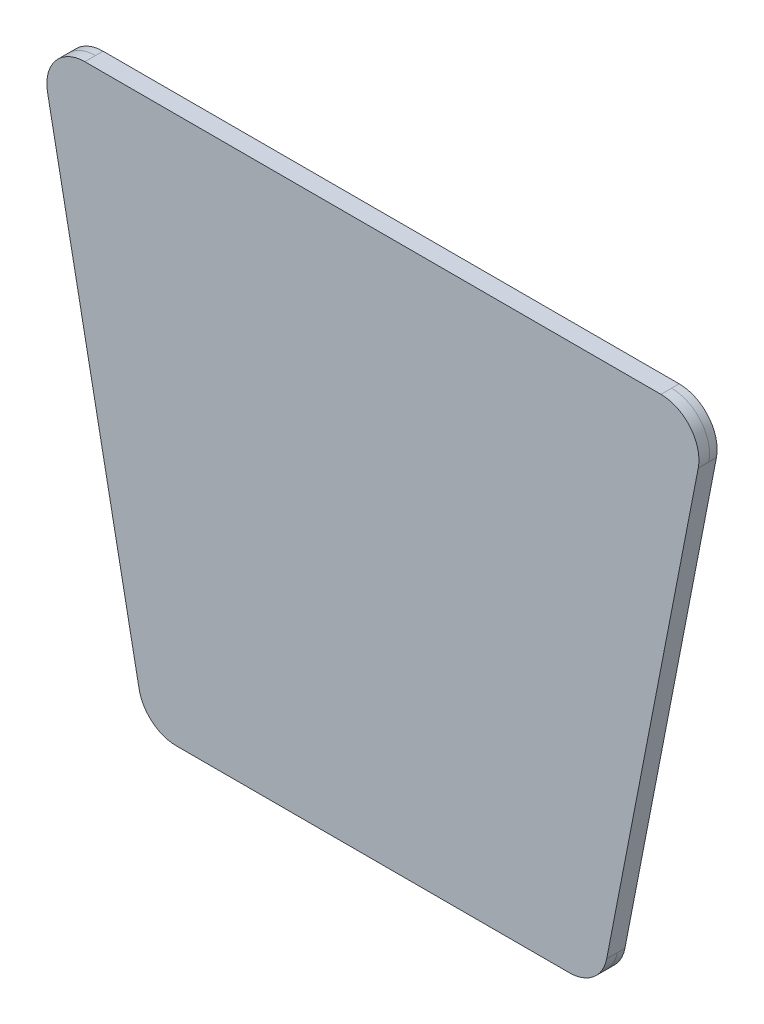
SolidWorks part; units mm, degrees
material "ABS PC"
ref_plane "Front Plane" through (0, 0, 0) normal (0, 0, 1) x (1, 0, 0)
ref_plane "Top Plane" through (0, 0, 0) normal (0, 1, 0) x (1, 0, 0)
ref_plane "Right Plane" through (0, 0, 0) normal (1, 0, 0) x (0, 0, -1)
sketch "Sketch1" plane through (0, 0, 0) normal (0, 0, 1) x (1, 0, 0)
  line L0 (-220, 0) -> (220, 0)
  line L1 (220, 0) -> (150, -360)
  line L2 (150, -360) -> (-150, -360)
  line L3 (-150, -360) -> (-220, 0)
  line L4 (0, 290.8745) -> (0, -449.6578) construction
  point P7 (185, -180)
  point P8 (-185, -180)
  dimension "D1" = 360
  dimension "D2" = 370
  dimension "D3" = 440
extrude "Boss-Extrude2" add sketch "Sketch1" along normal blind 12 contours L3 L0 L1 L2
fillet "Fillet1" radius 25 4 edges at (220, 0, 6) (150, -360, 6) (-220, 0, 6) (-150, -360, 6)
sketch "Sketch3" plane through (0, 0, 0) normal (0, 0, -1) x (-1, 0, 0)
  line L0 (189.6707, -2) -> (-189.6707, -2)
  line L1 (-212.2478, -29.39) -> (-151.97, -339.39)
  line L2 (-129.3929, -358) -> (129.3929, -358)
  line L3 (151.97, -339.39) -> (212.2478, -29.39)
  line L4 (189.6707, 0) -> (-189.6707, 0)
  line L5 (-214.2111, -29.7717) -> (-153.9333, -339.7717)
  line L6 (-129.3929, -360) -> (129.3929, -360)
  line L7 (153.9333, -339.7717) -> (214.2111, -29.7717)
  line L8 (189.6707, 0) -> (-189.6707, 0)
  line L9 (-214.2111, -29.7717) -> (-153.9333, -339.7717)
  line L10 (-129.3929, -360) -> (129.3929, -360)
  line L11 (153.9333, -339.7717) -> (214.2111, -29.7717)
  arc A0 (-189.6707, -2) -> (-212.2478, -29.39) centre (-189.6707, -25) ccw
  arc A1 (-151.97, -339.39) -> (-129.3929, -358) centre (-129.3929, -335) ccw
  arc A2 (129.3929, -358) -> (151.97, -339.39) centre (129.3929, -335) ccw
  arc A3 (212.2478, -29.39) -> (189.6707, -2) centre (189.6707, -25) ccw
  arc A4 (-189.6707, 0) -> (-214.2111, -29.7717) centre (-189.6707, -25) ccw
  arc A5 (-153.9333, -339.7717) -> (-129.3929, -360) centre (-129.3929, -335) ccw
  arc A6 (129.3929, -360) -> (153.9333, -339.7717) centre (129.3929, -335) ccw
  arc A7 (214.2111, -29.7717) -> (189.6707, 0) centre (189.6707, -25) ccw
  arc A8 (-189.6707, 0) -> (-214.2111, -29.7717) centre (-189.6707, -25) ccw
  arc A9 (-153.9333, -339.7717) -> (-129.3929, -360) centre (-129.3929, -335) ccw
  arc A10 (129.3929, -360) -> (153.9333, -339.7717) centre (129.3929, -335) ccw
  arc A11 (214.2111, -29.7717) -> (189.6707, 0) centre (189.6707, -25) ccw
  dimension "D1" = 0
  dimension "D2" = 2
extrude "Cut-Extrude1" cut sketch "Sketch3" against normal blind 10 contours L0 A0 L1 A1 L2 A2 L3 A3
sketch "Sketch4" plane through (0, 0, 10) normal (0, 0, -1) x (-1, 0, 0)
  circle A0 centre (-189.6707, -25) radius 23
  circle A1 centre (-189.6707, -25) radius 19
  dimension "D1" = 38
extrude "Boss-Extrude5" add sketch "Sketch4" along normal blind 10
sketch "Sketch5" plane through (0, 0, 10) normal (0, 0, -1) x (-1, 0, 0)
  circle A0 centre (-129.3929, -335) radius 23
  circle A1 centre (-129.3929, -335) radius 19
  dimension "D1" = 38
extrude "Boss-Extrude6" add sketch "Sketch5" along normal blind 10
mirror "Mirror1" about plane through (0, 0, 0) normal (1, 0, 0) of "Boss-Extrude6", "Boss-Extrude5"
ref_plane "Plane1" through (0, 0, 6) normal (0, 0, 1) x (1, 0, 0)
sketch "Sketch9" plane through (0, 0, 6) normal (0, 0, 1) x (1, 0, 0)
  line L0 (-182.9625, -180) -> (182.9625, -180) construction
  line L1 (25, -180) -> (17.6777, -162.3223) construction
  line L2 (17.6777, -162.3223) -> (0, -155) construction
  line L3 (0, -155) -> (-17.6777, -162.3223) construction
  line L4 (-17.6777, -162.3223) -> (-25, -180) construction
  line L5 (-25, -180) -> (-17.6777, -197.6777) construction
  line L6 (-17.6777, -197.6777) -> (0, -205) construction
  line L7 (0, -205) -> (17.6777, -197.6777) construction
  line L8 (17.6777, -197.6777) -> (25, -180) construction
  line L9 (0, -358) -> (0, -2) construction
  line L12 (-1, -2) -> (-1, -358)
  line L13 (1, -2) -> (1, -358)
  line L14 (-179.4142, -2) -> (130.6185, -312.0327)
  line L15 (-132.168, -312.168) -> (178, -2) construction
  line L16 (176.5858, -2) -> (-133.8503, -312.4361)
  line L17 (179.4142, -2) -> (-130.6185, -312.0327)
  line L18 (182.7681, -181) -> (-182.7681, -181)
  line L19 (-183.157, -179) -> (183.157, -179)
  line L20 (129.3929, -358) -> (-129.3929, -358) construction
  line L21 (-151.97, -339.39) -> (-212.2478, -29.39) construction
  line L22 (-189.6707, -2) -> (189.6707, -2) construction
  line L23 (212.2478, -29.39) -> (151.97, -339.39) construction
  line L24 (129.3929, -358) -> (-129.3929, -358)
  line L25 (-151.97, -339.39) -> (-212.2478, -29.39)
  line L26 (-189.6707, -2) -> (189.6707, -2)
  line L27 (212.2478, -29.39) -> (151.97, -339.39)
  line L29 (132.6318, -312.2292) -> (-184.3863, 4.7889) construction
  line L30 (133.8503, -312.4361) -> (-176.5858, -2)
  circle A0 centre (0, -180) radius 23.097 construction
  arc A1 (151.97, -339.39) -> (129.3929, -358) centre (129.3929, -335) ccw construction
  arc A2 (-129.3929, -358) -> (-151.97, -339.39) centre (-129.3929, -335) ccw construction
  arc A3 (-212.2478, -29.39) -> (-189.6707, -2) centre (-189.6707, -25) ccw construction
  arc A4 (189.6707, -2) -> (212.2478, -29.39) centre (189.6707, -25) ccw construction
  arc A5 (151.97, -339.39) -> (129.3929, -358) centre (129.3929, -335) ccw
  arc A6 (-129.3929, -358) -> (-151.97, -339.39) centre (-129.3929, -335) ccw
  arc A7 (-212.2478, -29.39) -> (-189.6707, -2) centre (-189.6707, -25) ccw
  arc A8 (189.6707, -2) -> (212.2478, -29.39) centre (189.6707, -25) ccw
  point P14 (0, -180)
  point P17 (0, -180)
  point P20 (0, -180)
  point P23 (0, -180)
  dimension "D1" = 180
  dimension "D2" = 25
  dimension "D3" = 2
  dimension "D4" = 2
  dimension "D5" = 2
  dimension "D6" = 2
  dimension "D7" = 130.6185
extrude "Boss-Extrude9" add sketch "Sketch9" along normal up to surface (4 mm away) contours L13 L30 L19 L16 L12 L14 L18 L17 | L19 L30 L16 | L30 L13 L19 | L17 L30 L13 | L17 L18 L14 | L18 L14 L12 | L12 L16 L14 | L14 L18 L12 L17 | L18 L12 L14 L16 | L19 L14 L16 L12 | L19 L12 L16 | L16 L30 L12 L19 | L30 L19 L13 L16 | L30 L17 L19 L13 | L18 L30 L17 L13 | L18 L13 L17 | L13 L18 L17 L14 | A5 L30 L18 L13 L14 | L24 L13 L14 L17 L12 | A6 L17 L12 L18 L16 | L25 L18 L16 L14 L19 | L12 L30 L26 L14 L19 | L30 L16 L13 L26 L12 | L26 L16 L13 L19 L17 | L30 L18 L27 L19 L17 region at (0, -90.0431, 6) region at (-0.6381, -178.4596, 6) region at (-89.6781, -90.3238, 6) region at (-0.8047, -179.1953, 6) region at (-1.5404, -179.3619, 6) region at (0, -178.8619, 6) region at (0.6381, -178.4596, 6) region at (89.6781, -90.3238, 6) region at (0, -180, 6) region at (-1.1381, -180, 6) region at (-92.4382, -179.9996, 6) region at (0.8047, -179.1953, 6) region at (1.5404, -179.3619, 6) region at (-0.8047, -180.8047, 6) region at (-1.5404, -180.6381, 6) region at (1.1381, -180, 6) region at (92.4382, -179.9996, 6) region at (-0.6381, -181.5404, 6) region at (-66.7743, -246.7711, 6) region at (0, -181.1381, 6) region at (1.5404, -180.6381, 6) region at (0.8047, -180.8047, 6) region at (0, -269.9569, 6) region at (0.6381, -181.5404, 6) region at (66.7743, -246.7711, 6) up to face at (0, -180.3179, 10)
sketch "Sketch10" plane through (0, 0, 6) normal (0, 0, 1) x (1, 0, 0)
  line L0 (182.7681, -181) -> (-182.7681, -181) construction
  line L1 (179.4142, -2) -> (-130.6185, -312.0327) construction
  line L2 (-183.157, -179) -> (183.157, -179) construction
  line L3 (176.5858, -2) -> (-133.8503, -312.4361) construction
  line L4 (-212.2478, -29.39) -> (-151.97, -339.39)
  line L5 (-129.3929, -358) -> (129.3929, -358)
  line L6 (151.97, -339.39) -> (212.2478, -29.39)
  line L7 (189.6707, -2) -> (-189.6707, -2)
  line L8 (-212.2478, -29.39) -> (-151.97, -339.39)
  line L9 (-129.3929, -358) -> (129.3929, -358)
  line L10 (151.97, -339.39) -> (212.2478, -29.39)
  line L11 (189.6707, -2) -> (-189.6707, -2)
  line L12 (-179.4142, -2) -> (130.6185, -312.0327) construction
  line L13 (1, -2) -> (1, -358) construction
  line L14 (-1, -2) -> (-1, -358) construction
  line L15 (133.8503, -312.4361) -> (-176.5858, -2) construction
  line L16 (182.7681, -181) -> (-182.7681, -181)
  line L17 (179.4142, -2) -> (-130.6185, -312.0327)
  line L18 (-183.157, -179) -> (183.157, -179)
  line L19 (176.5858, -2) -> (-133.8503, -312.4361)
  line L20 (-179.4142, -2) -> (130.6185, -312.0327)
  line L21 (1, -2) -> (1, -358)
  line L22 (-1, -2) -> (-1, -358)
  line L23 (133.8503, -312.4361) -> (-176.5858, -2)
  line L24 (0, 33.3188) -> (0, -390.4492) construction
  line L25 (189.9291, -180) -> (-188.2058, -180) construction
  line L26 (-189.6707, 0) -> (189.6707, 0) construction
  line L36 (0, -151.8578) -> (-19.8995, -160.1005) construction
  line L37 (-19.8995, -160.1005) -> (-28.1422, -180) construction
  line L38 (-28.1422, -180) -> (-19.8995, -199.8995) construction
  line L39 (-19.8995, -199.8995) -> (0, -208.1422) construction
  line L40 (0, -208.1422) -> (19.8995, -199.8995) construction
  line L41 (19.8995, -199.8995) -> (28.1422, -180) construction
  line L42 (28.1422, -180) -> (19.8995, -160.1005) construction
  line L43 (19.8995, -160.1005) -> (0, -151.8578) construction
  line L44 (0, -154.0226) -> (-18.3688, -161.6312) construction
  line L45 (-18.3688, -161.6312) -> (-25.9774, -180) construction
  line L46 (-25.9774, -180) -> (-18.3688, -198.3688) construction
  line L47 (-18.3688, -198.3688) -> (0, -205.9774) construction
  line L48 (0, -205.9774) -> (18.3688, -198.3688) construction
  line L49 (18.3688, -198.3688) -> (25.9774, -180) construction
  line L50 (25.9774, -180) -> (18.3688, -161.6312) construction
  line L51 (18.3688, -161.6312) -> (0, -154.0226) construction
  line L52 (0, -137.7867) -> (-29.8493, -150.1507) construction
  line L53 (-29.8493, -150.1507) -> (-42.2133, -180) construction
  line L54 (-42.2133, -180) -> (-29.8493, -209.8493) construction
  line L55 (-29.8493, -209.8493) -> (0, -222.2133) construction
  line L56 (0, -222.2133) -> (29.8493, -209.8493) construction
  line L57 (29.8493, -209.8493) -> (42.2133, -180) construction
  line L58 (42.2133, -180) -> (29.8493, -150.1507) construction
  line L59 (29.8493, -150.1507) -> (0, -137.7867) construction
  line L60 (0, -135.6219) -> (-31.38, -148.62) construction
  line L61 (-31.38, -148.62) -> (-44.3781, -180) construction
  line L62 (-44.3781, -180) -> (-31.38, -211.38) construction
  line L63 (-31.38, -211.38) -> (0, -224.3781) construction
  line L64 (0, -224.3781) -> (31.38, -211.38) construction
  line L65 (31.38, -211.38) -> (44.3781, -180) construction
  line L66 (44.3781, -180) -> (31.38, -148.62) construction
  line L67 (31.38, -148.62) -> (0, -135.6219) construction
  line L68 (0, -116.1389) -> (-45.1566, -134.8434) construction
  line L69 (-45.1566, -134.8434) -> (-63.8611, -180) construction
  line L70 (-63.8611, -180) -> (-45.1566, -225.1566) construction
  line L71 (-45.1566, -225.1566) -> (0, -243.8611) construction
  line L72 (0, -243.8611) -> (45.1566, -225.1566) construction
  line L73 (45.1566, -225.1566) -> (63.8611, -180) construction
  line L74 (63.8611, -180) -> (45.1566, -134.8434) construction
  line L75 (45.1566, -134.8434) -> (0, -116.1389) construction
  line L76 (-66.0259, -180) -> (-46.6874, -226.6874) construction
  line L77 (-46.6874, -226.6874) -> (0, -246.0259) construction
  line L78 (0, -246.0259) -> (46.6874, -226.6874) construction
  line L79 (46.6874, -226.6874) -> (66.0259, -180) construction
  line L80 (66.0259, -180) -> (46.6874, -133.3126) construction
  line L81 (46.6874, -133.3126) -> (0, -113.9741) construction
  line L82 (0, -113.9741) -> (-46.6874, -133.3126) construction
  line L83 (-46.6874, -133.3126) -> (-66.0259, -180) construction
  line L84 (0, -83.6671) -> (-68.1177, -111.8823) construction
  line L85 (-68.1177, -111.8823) -> (-96.3329, -180) construction
  line L86 (-96.3329, -180) -> (-68.1177, -248.1177) construction
  line L87 (-68.1177, -248.1177) -> (0, -276.3329) construction
  line L88 (0, -276.3329) -> (68.1177, -248.1177) construction
  line L89 (68.1177, -248.1177) -> (96.3329, -180) construction
  line L90 (96.3329, -180) -> (68.1177, -111.8823) construction
  line L91 (68.1177, -111.8823) -> (0, -83.6671) construction
  line L92 (0, -81.5023) -> (-69.6484, -110.3516) construction
  line L93 (-69.6484, -110.3516) -> (-98.4977, -180) construction
  line L94 (-98.4977, -180) -> (-69.6484, -249.6484) construction
  line L95 (-69.6484, -249.6484) -> (0, -278.4977) construction
  line L96 (0, -278.4977) -> (69.6484, -249.6484) construction
  line L97 (69.6484, -249.6484) -> (98.4977, -180) construction
  line L98 (98.4977, -180) -> (69.6484, -110.3516) construction
  line L99 (69.6484, -110.3516) -> (0, -81.5023) construction
  line L100 (0, -40.3714) -> (-98.7323, -81.2677) construction
  line L101 (-98.7323, -81.2677) -> (-139.6286, -180) construction
  line L102 (-139.6286, -180) -> (-98.7323, -278.7323) construction
  line L103 (-98.7323, -278.7323) -> (0, -319.6286) construction
  line L104 (0, -319.6286) -> (98.7323, -278.7323) construction
  line L105 (98.7323, -278.7323) -> (139.6286, -180) construction
  line L106 (139.6286, -180) -> (98.7323, -81.2677) construction
  line L107 (98.7323, -81.2677) -> (0, -40.3714) construction
  line L108 (0, -38.2066) -> (-100.2631, -79.7369) construction
  line L109 (-100.2631, -79.7369) -> (-141.7934, -180) construction
  line L110 (-141.7934, -180) -> (-100.2631, -280.2631) construction
  line L111 (-100.2631, -280.2631) -> (0, -321.7934) construction
  line L112 (0, -321.7934) -> (100.2631, -280.2631) construction
  line L113 (100.2631, -280.2631) -> (141.7934, -180) construction
  line L114 (141.7934, -180) -> (100.2631, -79.7369) construction
  line L115 (100.2631, -79.7369) -> (0, -38.2066) construction
  line L116 (0, -7.8996) -> (-121.6933, -58.3067) construction
  line L117 (-121.6933, -58.3067) -> (-172.1004, -180) construction
  line L118 (-172.1004, -180) -> (-121.6933, -301.6933) construction
  line L119 (-121.6933, -301.6933) -> (0, -352.1004) construction
  line L120 (0, -352.1004) -> (121.6933, -301.6933) construction
  line L121 (121.6933, -301.6933) -> (172.1004, -180) construction
  line L122 (172.1004, -180) -> (121.6933, -58.3067) construction
  line L123 (121.6933, -58.3067) -> (0, -7.8996) construction
  line L124 (0, -5.7349) -> (-123.2241, -56.7759) construction
  line L125 (-123.2241, -56.7759) -> (-174.2651, -180) construction
  line L126 (-174.2651, -180) -> (-123.2241, -303.2241) construction
  line L127 (-123.2241, -303.2241) -> (0, -354.2651) construction
  line L128 (0, -354.2651) -> (123.2241, -303.2241) construction
  line L129 (123.2241, -303.2241) -> (174.2651, -180) construction
  line L130 (174.2651, -180) -> (123.2241, -56.7759) construction
  line L131 (123.2241, -56.7759) -> (0, -5.7349) construction
  arc A0 (0, -151.8578) -> (-19.8995, -160.1005) centre (-31.9509, -102.8638) cw
  circle A1 centre (0, -180) radius 26 construction
  circle A2 centre (0, -180) radius 24 construction
  arc A3 (0, -154.0226) -> (-18.3688, -161.6312) centre (-27.9026, -112.6372) cw
  arc A4 (-129.3929, -358) -> (-151.97, -339.39) centre (-129.3929, -335) ccw
  arc A5 (151.97, -339.39) -> (129.3929, -358) centre (129.3929, -335) ccw
  arc A6 (189.6707, -2) -> (212.2478, -29.39) centre (189.6707, -25) ccw
  arc A7 (-212.2478, -29.39) -> (-189.6707, -2) centre (-189.6707, -25) ccw
  arc A8 (-129.3929, -358) -> (-151.97, -339.39) centre (-129.3929, -335) ccw
  arc A9 (151.97, -339.39) -> (129.3929, -358) centre (129.3929, -335) ccw
  arc A10 (189.6707, -2) -> (212.2478, -29.39) centre (189.6707, -25) ccw
  arc A11 (-212.2478, -29.39) -> (-189.6707, -2) centre (-189.6707, -25) ccw
  arc A12 (0, -151.8578) -> (19.8995, -160.1005) centre (31.9509, -102.8638) ccw
  arc A13 (18.3688, -161.6312) -> (0, -154.0226) centre (27.9026, -112.6372) cw
  arc A14 (18.3688, -161.6312) -> (25.9774, -180) centre (67.3628, -152.0974) ccw
  arc A15 (25.9774, -180) -> (18.3688, -198.3688) centre (67.3628, -207.9026) ccw
  arc A16 (18.3688, -198.3688) -> (0, -205.9774) centre (27.9026, -247.3628) ccw
  arc A17 (0, -205.9774) -> (-18.3688, -198.3688) centre (-27.9026, -247.3628) ccw
  arc A18 (-18.3688, -198.3688) -> (-25.9774, -180) centre (-67.3628, -207.9026) ccw
  arc A19 (-25.9774, -180) -> (-18.3688, -161.6312) centre (-67.3628, -152.0974) ccw
  arc A20 (-19.8995, -160.1005) -> (-28.1422, -180) centre (-77.1362, -148.0491) cw
  arc A21 (-28.1422, -180) -> (-19.8995, -199.8995) centre (-77.1362, -211.9509) cw
  arc A22 (-19.8995, -199.8995) -> (0, -208.1422) centre (-31.9509, -257.1362) cw
  arc A23 (0, -208.1422) -> (19.8995, -199.8995) centre (31.9509, -257.1362) cw
  arc A24 (19.8995, -199.8995) -> (28.1422, -180) centre (77.1362, -211.9509) cw
  arc A25 (28.1422, -180) -> (19.8995, -160.1005) centre (77.1362, -148.0491) cw
  circle A26 centre (0, -180) radius 39 construction
  circle A27 centre (0, -180) radius 41 construction
  arc A28 (0, -135.6219) -> (-31.38, -148.62) centre (-70.6843, -9.353) cw
  arc A29 (-31.38, -148.62) -> (-44.3781, -180) centre (-170.647, -109.3157) cw
  arc A30 (-44.3781, -180) -> (-31.38, -211.38) centre (-170.647, -250.6843) cw
  arc A31 (-31.38, -211.38) -> (0, -224.3781) centre (-70.6843, -350.647) cw
  arc A32 (0, -224.3781) -> (31.38, -211.38) centre (70.6843, -350.647) cw
  arc A33 (31.38, -211.38) -> (44.3781, -180) centre (170.647, -250.6843) cw
  arc A34 (44.3781, -180) -> (31.38, -148.62) centre (170.647, -109.3157) cw
  arc A35 (31.38, -148.62) -> (0, -135.6219) centre (70.6843, -9.353) cw
  arc A36 (0, -137.7867) -> (-29.8493, -150.1507) centre (-64.6663, -23.8818) cw
  arc A37 (-29.8493, -150.1507) -> (-42.2133, -180) centre (-156.1182, -115.3337) cw
  arc A38 (-42.2133, -180) -> (-29.8493, -209.8493) centre (-156.1182, -244.6663) cw
  arc A39 (-29.8493, -209.8493) -> (0, -222.2133) centre (-64.6663, -336.1182) cw
  arc A40 (0, -222.2133) -> (29.8493, -209.8493) centre (64.6663, -336.1182) cw
  arc A41 (29.8493, -209.8493) -> (42.2133, -180) centre (156.1182, -244.6663) cw
  arc A42 (42.2133, -180) -> (29.8493, -150.1507) centre (156.1182, -115.3337) cw
  arc A43 (29.8493, -150.1507) -> (0, -137.7867) centre (64.6663, -23.8818) cw
  circle A44 centre (0, -180) radius 59 construction
  circle A45 centre (0, -180) radius 61 construction
  arc A46 (0, -113.9741) -> (-46.6874, -133.3126) centre (-145.3092, 170.8075) cw
  arc A47 (-46.6874, -133.3126) -> (-66.0259, -180) centre (-350.8075, -34.6908) cw
  arc A48 (-66.0259, -180) -> (-46.6874, -226.6874) centre (-350.8075, -325.3092) cw
  arc A49 (-46.6874, -226.6874) -> (0, -246.0259) centre (-145.3092, -530.8075) cw
  arc A50 (0, -246.0259) -> (46.6874, -226.6874) centre (145.3092, -530.8075) cw
  arc A51 (46.6874, -226.6874) -> (66.0259, -180) centre (350.8075, -325.3092) cw
  arc A52 (66.0259, -180) -> (46.6874, -133.3126) centre (350.8075, -34.6908) cw
  arc A53 (46.6874, -133.3126) -> (0, -113.9741) centre (145.3092, 170.8075) cw
  arc A54 (0, -116.1389) -> (-45.1566, -134.8434) centre (-136.6649, 149.9383) cw
  arc A55 (-45.1566, -134.8434) -> (-63.8611, -180) centre (-329.9383, -43.3351) cw
  arc A56 (-63.8611, -180) -> (-45.1566, -225.1566) centre (-329.9383, -316.6649) cw
  arc A57 (-45.1566, -225.1566) -> (0, -243.8611) centre (-136.6649, -509.9383) cw
  arc A58 (0, -243.8611) -> (45.1566, -225.1566) centre (136.6649, -509.9383) cw
  arc A59 (45.1566, -225.1566) -> (63.8611, -180) centre (329.9383, -316.6649) cw
  arc A60 (63.8611, -180) -> (45.1566, -134.8434) centre (329.9383, -43.3351) cw
  arc A61 (45.1566, -134.8434) -> (0, -116.1389) centre (136.6649, 149.9383) cw
  circle A62 centre (0, -180) radius 89 construction
  circle A63 centre (0, -180) radius 91 construction
  arc A64 (0, -81.5023) -> (-69.6484, -110.3516) centre (-306.4902, 559.9328) cw
  arc A65 (-69.6484, -110.3516) -> (-98.4977, -180) centre (-739.9328, 126.4902) cw
  arc A66 (-98.4977, -180) -> (-69.6484, -249.6484) centre (-739.9328, -486.4902) cw
  arc A67 (-69.6484, -249.6484) -> (0, -278.4977) centre (-306.4902, -919.9328) cw
  arc A68 (0, -276.3329) -> (-68.1177, -248.1177) centre (-293.9064, -889.5528) ccw
  arc A69 (-68.1177, -248.1177) -> (-96.3329, -180) centre (-709.5528, -473.9064) ccw
  arc A70 (-96.3329, -180) -> (-68.1177, -111.8823) centre (-709.5528, 113.9064) ccw
  arc A71 (-68.1177, -111.8823) -> (0, -83.6671) centre (-293.9064, 529.5528) ccw
  arc A72 (69.6484, -249.6484) -> (0, -278.4977) centre (306.4902, -919.9328) ccw
  arc A73 (0, -276.3329) -> (68.1177, -248.1177) centre (293.9064, -889.5528) cw
  arc A74 (68.1177, -248.1177) -> (96.3329, -180) centre (709.5528, -473.9064) cw
  arc A75 (98.4977, -180) -> (69.6484, -249.6484) centre (739.9328, -486.4902) ccw
  arc A76 (69.6484, -110.3516) -> (98.4977, -180) centre (739.9328, 126.4902) ccw
  arc A77 (96.3329, -180) -> (68.1177, -111.8823) centre (709.5528, 113.9064) cw
  arc A78 (68.1177, -111.8823) -> (0, -83.6671) centre (293.9064, 529.5528) cw
  arc A79 (0, -81.5023) -> (69.6484, -110.3516) centre (306.4902, 559.9328) ccw
  circle A80 centre (0, -180) radius 129 construction
  circle A81 centre (0, -180) radius 131 construction
  arc A82 (0, -38.2066) -> (-100.2631, -79.7369) centre (-613.3195, 1300.6842) cw
  arc A83 (-100.2631, -79.7369) -> (-141.7934, -180) centre (-1480.6842, 433.3195) cw
  arc A84 (-141.7934, -180) -> (-100.2631, -280.2631) centre (-1480.6842, -793.3195) cw
  arc A85 (-100.2631, -280.2631) -> (0, -321.7934) centre (-613.3195, -1660.6842) cw
  arc A86 (0, -319.6286) -> (-98.7323, -278.7323) centre (-595.483, -1617.6232) ccw
  arc A87 (-98.7323, -278.7323) -> (-139.6286, -180) centre (-1437.6232, -775.483) ccw
  arc A88 (-139.6286, -180) -> (-98.7323, -81.2677) centre (-1437.6232, 415.483) ccw
  arc A89 (-98.7323, -81.2677) -> (0, -40.3714) centre (-595.483, 1257.6232) ccw
  arc A90 (100.2631, -79.7369) -> (141.7934, -180) centre (1480.6842, 433.3195) ccw
  arc A91 (139.6286, -180) -> (98.7323, -81.2677) centre (1437.6232, 415.483) cw
  arc A92 (0, -38.2066) -> (100.2631, -79.7369) centre (613.3195, 1300.6842) ccw
  arc A93 (98.7323, -81.2677) -> (0, -40.3714) centre (595.483, 1257.6232) cw
  arc A94 (141.7934, -180) -> (100.2631, -280.2631) centre (1480.6842, -793.3195) ccw
  arc A95 (98.7323, -278.7323) -> (139.6286, -180) centre (1437.6232, -775.483) cw
  arc A96 (100.2631, -280.2631) -> (0, -321.7934) centre (613.3195, -1660.6842) ccw
  arc A97 (0, -319.6286) -> (98.7323, -278.7323) centre (595.483, -1617.6232) cw
  circle A98 centre (0, -180) radius 159 construction
  circle A99 centre (0, -180) radius 161 construction
  arc A100 (0, -5.7349) -> (-123.2241, -56.7759) centre (-912.3825, 2022.6861) cw
  arc A101 (-123.2241, -56.7759) -> (-174.2651, -180) centre (-2202.6861, 732.3825) cw
  arc A102 (-174.2651, -180) -> (-123.2241, -303.2241) centre (-2202.6861, -1092.3825) cw
  arc A103 (-123.2241, -303.2241) -> (0, -354.2651) centre (-912.3825, -2382.6861) cw
  arc A104 (0, -352.1004) -> (-121.6933, -301.6933) centre (-890.6065, -2330.1143) ccw
  arc A105 (-121.6933, -301.6933) -> (-172.1004, -180) centre (-2150.1143, -1070.6065) ccw
  arc A106 (-172.1004, -180) -> (-121.6933, -58.3067) centre (-2150.1143, 710.6065) ccw
  arc A107 (-121.6933, -58.3067) -> (0, -7.8996) centre (-890.6065, 1970.1143) ccw
  arc A108 (123.2241, -56.7759) -> (174.2651, -180) centre (2202.6861, 732.3825) ccw
  arc A109 (172.1004, -180) -> (121.6933, -58.3067) centre (2150.1143, 710.6065) cw
  arc A110 (121.6933, -58.3067) -> (0, -7.8996) centre (890.6065, 1970.1143) cw
  arc A111 (0, -5.7349) -> (123.2241, -56.7759) centre (912.3825, 2022.6861) ccw
  arc A112 (121.6933, -301.6933) -> (172.1004, -180) centre (2150.1143, -1070.6065) cw
  arc A113 (174.2651, -180) -> (123.2241, -303.2241) centre (2202.6861, -1092.3825) ccw
  arc A114 (123.2241, -303.2241) -> (0, -354.2651) centre (912.3825, -2382.6861) ccw
  arc A115 (0, -352.1004) -> (121.6933, -301.6933) centre (890.6065, -2330.1143) cw
  dimension "D3" = 1
  dimension "D5" = 1
  dimension "D6" = 24
  dimension "D7" = 1
  dimension "D8" = 1
  dimension "D9" = 1
  dimension "D10" = 1
  dimension "D11" = 1
  dimension "D12" = 1
  dimension "D13" = 1
  dimension "D14" = 1
  dimension "D15" = 1
  dimension "D16" = 1
  dimension "D17" = 1
  dimension "D18" = 1
  dimension "D19" = 1
  dimension "D20" = 1
  dimension "D21" = 2
  dimension "D22" = 15
  dimension "D24" = 1
  dimension "D26" = 1
  dimension "D27" = 1
  dimension "D28" = 1
  dimension "D29" = 1
  dimension "D30" = 1
  dimension "D31" = 1
  dimension "D32" = 1
  dimension "D33" = 1
  dimension "D34" = 1
  dimension "D35" = 1
  dimension "D36" = 1
  dimension "D37" = 1
  dimension "D38" = 1
  dimension "D41" = 1
  dimension "D42" = 1
  dimension "D43" = 1
  dimension "D44" = 1
  dimension "D45" = 1
  dimension "D46" = 1
  dimension "D47" = 1
  dimension "D48" = 1
  dimension "D49" = 1
  dimension "D50" = 1
  dimension "D51" = 1
  dimension "D52" = 1
  dimension "D53" = 1
  dimension "D54" = 1
  dimension "D55" = 1
  dimension "D56" = 1
  dimension "D57" = 30
  dimension "D59" = 1
  dimension "D60" = 1
  dimension "D61" = 1
  dimension "D62" = 1
  dimension "D63" = 1
  dimension "D64" = 1
  dimension "D65" = 1
  dimension "D66" = 1
  dimension "D67" = 710.8975
  dimension "D68" = 680.0144
  dimension "D71" = 1
  dimension "D72" = 1
  dimension "D73" = 1
  dimension "D74" = 1
  dimension "D75" = 1
  dimension "D76" = 1
  dimension "D77" = 1
  dimension "D78" = 1
  dimension "D79" = 1472.6811
  dimension "D80" = 1428.0721
  dimension "D83" = 1
  dimension "D84" = 1
  dimension "D85" = 1
  dimension "D86" = 1
  dimension "D87" = 1
  dimension "D88" = 1
  dimension "D89" = 1
  dimension "D90" = 1
  dimension "D2" = 180
  dimension "D4" = 2
  dimension "D23" = 1
  dimension "D25" = 1
  dimension "D39" = 20
  dimension "D40" = 2
  dimension "D58" = 2
  dimension "D69" = 40
  dimension "D70" = 40
  dimension "D81" = 30
  dimension "D82" = 30
  dimension "D1" = 0
extrude "Boss-Extrude11" add sketch "Sketch10" along normal up to surface (4 mm away) contours A13 L19 A12 L21 | L18 A25 L17 A14 | A3 L22 A0 L23 | L20 A20 L18 A19 | L16 A21 L19 A18 | L17 A22 L22 A17 | L21 A23 L20 A16 | L23 A24 L16 A15 region at (-22.4242, -170.7116, 6) region at (-22.4242, -189.2884, 6) region at (-9.2884, -157.5758, 6) region at (-9.2884, -202.4242, 6) region at (9.2884, -157.5758, 6) region at (22.4242, -170.7116, 6) region at (9.2884, -202.4242, 6) region at (22.4242, -189.2884, 6) up to face at (-59.6017, -302.4544, 10)
extrude "Boss-Extrude12" add sketch "Sketch10<6>" along normal up to surface (4 mm away) contours A43 L19 A35 L21 | A42 L18 A34 L17 | A36 L22 A28 L23 | A37 L20 A29 L18 | A38 L16 A30 L19 | A39 L17 A31 L22 | A40 L21 A32 L20 | A41 L23 A33 L16 region at (-36.3032, -164.9627, 6) region at (-36.3032, -195.0373, 6) region at (-15.0373, -143.6968, 6) region at (-15.0373, -216.3032, 6) region at (15.0373, -143.6968, 6) region at (36.3032, -164.9627, 6) region at (15.0373, -216.3032, 6) region at (36.3032, -195.0373, 6) up to face at (130.3967, -96.1477, 10)
sketch "Sketch10<6>" plane through (0, 0, 6) normal (0, 0, 1) x (1, 0, 0) same geometry as "Sketch10"
extrude "Boss-Extrude13" add sketch "Sketch10<7>" along normal up to surface (4 mm away) contours A61 L19 A53 L21 | A60 L18 A52 L17 | A59 L23 A51 L16 | A58 L21 A50 L20 | A57 L17 A49 L22 | A56 L16 A48 L19 | A55 L20 A47 L18 | A54 L22 A46 L23 region at (-54.7927, -157.3041, 6) region at (-54.7927, -202.6959, 6) region at (-22.6959, -125.2073, 6) region at (-22.6959, -234.7927, 6) region at (22.6959, -125.2073, 6) region at (54.7927, -157.3041, 6) region at (22.6959, -234.7927, 6) region at (54.7927, -202.6959, 6) up to face at (-52.1334, -72.3214, 10)
sketch "Sketch10<7>" plane through (0, 0, 6) normal (0, 0, 1) x (1, 0, 0) same geometry as "Sketch10"
extrude "Boss-Extrude15" add sketch "Sketch10<9>" along normal up to surface (4 mm away) contours A73 L21 A72 L20 | A75 L16 A74 L23 | A77 L18 A76 L17 | A79 L21 A78 L19 | L23 A71 L22 A64 | L18 A70 L20 A65 | L19 A69 L16 A66 | L22 A68 L17 A67 region at (-82.5171, -145.8203, 6) region at (-82.5171, -214.1797, 6) region at (-34.1797, -97.4829, 6) region at (-34.1797, -262.5171, 6) region at (34.1797, -97.4829, 6) region at (82.5171, -145.8203, 6) region at (34.1797, -262.5171, 6) region at (82.5171, -214.1797, 6) up to face at (117.1737, -247.0706, 10)
sketch "Sketch10<9>" plane through (0, 0, 6) normal (0, 0, 1) x (1, 0, 0) same geometry as "Sketch10"
extrude "Boss-Extrude16" add sketch "Sketch10<10>" along normal up to surface (4 mm away) contours A95 L23 A94 L16 | A97 L21 A96 L20 | L22 A86 L17 A85 | L19 A87 L16 A84 | L18 A88 L20 A83 | L23 A89 L22 A82 | A93 L19 A92 L21 | A91 L18 A90 L17 region at (-119.4772, -130.5109, 6) region at (-119.4772, -229.4891, 6) region at (-49.4891, -60.5228, 6) region at (-49.4891, -299.4772, 6) region at (49.4891, -60.5228, 6) region at (119.4772, -130.5109, 6) region at (49.4891, -299.4772, 6) region at (119.4772, -229.4891, 6) up to face at (150.437, -87.8468, 10)
sketch "Sketch10<10>" plane through (0, 0, 6) normal (0, 0, 1) x (1, 0, 0) same geometry as "Sketch10"
extrude "Boss-Extrude17" add sketch "Sketch10<11>" along normal up to surface (4 mm away) contours A111 L21 A110 L19 | L23 A107 L22 A100 | L18 A106 L20 A101 | L19 A105 L16 A102 | L22 A104 L17 A103 | A115 L21 A114 L20 | A113 L16 A112 L23 | A109 L18 A108 L17 region at (-147.1957, -119.0296, 6) region at (-147.1957, -240.9704, 6) region at (-60.9704, -32.8043, 6) region at (-60.9704, -327.1957, 6) region at (60.9704, -32.8043, 6) region at (147.1957, -119.0296, 6) region at (60.9704, -327.1957, 6) region at (147.1957, -240.9704, 6) up to face at (162.7581, -82.7432, 10)
sketch "Sketch10<11>" plane through (0, 0, 6) normal (0, 0, 1) x (1, 0, 0) same geometry as "Sketch10"
sketch "Sketch11" plane through (0, 0, 0) normal (0, 0, 1) x (1, 0, 0)
  line L4 (220, 0) -> (-220, 0)
  line L5 (150, -360) -> (220, 0)
  line L6 (-150, -360) -> (150, -360)
  line L7 (-220, 0) -> (-150, -360)
  line L8 (220, 0) -> (-220, 0)
  line L9 (150, -360) -> (220, 0)
  line L10 (-150, -360) -> (150, -360)
  line L11 (-220, 0) -> (-150, -360)
  dimension "D1" = 0
extrude "Boss-Extrude18" add sketch "Sketch11" along normal blind 5
fillet "Fillet3" radius 25 4 edges at (-220, 0, 2.5) (-150, -360, 2.5) (150, -360, 2.5) (220, 0, 2.5)
